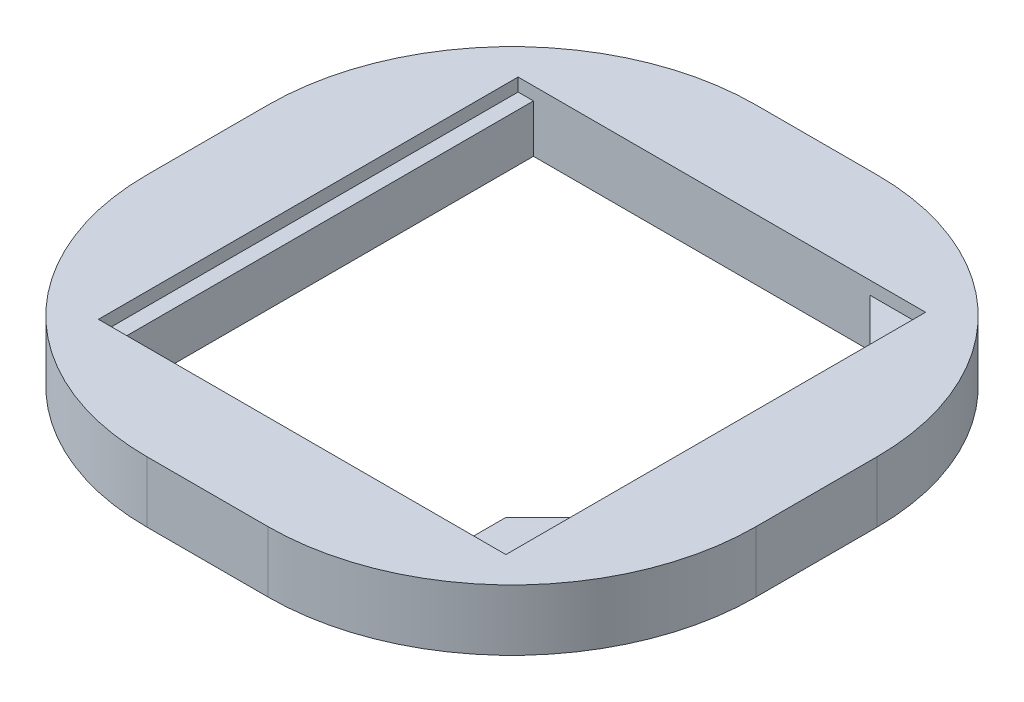
SolidWorks part; units mm, degrees
ref_plane "Front Plane" through (0, 0, 0) normal (0, 0, 1) x (1, 0, 0)
ref_plane "Top Plane" through (0, 0, 0) normal (0, 1, 0) x (1, 0, 0)
ref_plane "Right Plane" through (0, 0, 0) normal (1, 0, 0) x (0, 0, -1)
sketch "Sketch2" plane through (0, 0, 0) normal (0, 1, 0) x (1, 0, 0)
  line L1 (-37.45, -37.45) -> (37.45, -37.45)
  line L2 (-37.45, -37.45) -> (-37.45, 37.45)
  line L3 (-37.45, 37.45) -> (37.45, 37.45)
  line L4 (37.45, -37.45) -> (37.45, 37.45)
  line L5 (-37.45, -37.45) -> (37.45, 37.45) construction
  line L6 (-37.45, 37.45) -> (37.45, -37.45) construction
  point P0 (0, 0)
  dimension "D1" = 74.9
  dimension "D2" = 74.9
extrude "Base" add sketch "Sketch2" along normal blind 7.5
sketch "Sketch3" plane through (0, 7.5, 0) normal (0, 1, 0) x (1, 0, 0)
  line L1 (-25.05, -25.8) -> (25.05, -25.8)
  line L2 (-25.05, -25.8) -> (-25.05, 25.8)
  line L3 (-25.05, 25.8) -> (25.05, 25.8)
  line L4 (25.05, -25.8) -> (25.05, 25.8)
  line L5 (-25.05, -25.8) -> (25.05, 25.8) construction
  line L6 (-25.05, 25.8) -> (25.05, -25.8) construction
  point P0 (0, 0)
  dimension "D1" = 50.1
  dimension "D2" = 51.6
extrude "Slot" cut sketch "Sketch3" against normal blind 1.6
sketch "Sketch4" plane through (0, 5.9, 0) normal (0, 1, 0) x (1, 0, 0)
  line L0 (-23.1595, -25.8) -> (-23.1595, 25.8)
  line L1 (-23.1595, 25.8) -> (18.1922, 25.8)
  line L3 (18.1922, 25.8) -> (25.05, 18.9809)
  line L4 (25.05, 25.8) -> (-25.05, 25.8) construction
  line L5 (25.05, 18.9809) -> (25.05, -14.6954)
  line L6 (25.05, -25.8) -> (25.05, 25.8) construction
  line L7 (25.05, -14.6954) -> (19.4909, -20.2861)
  line L8 (19.4909, -20.2861) -> (19.4909, -25.8)
  line L9 (-25.05, -25.8) -> (25.05, -25.8) construction
  line L10 (19.4909, -25.8) -> (-23.1595, -25.8)
  line L11 (25.05, -25.8) -> (25.05, 25.8) construction
  point P2 (18.1922, 25.8)
extrude "Cut-Extrude2" cut sketch "Sketch4" against normal up to surface (5.9 mm away) up to face at (0, 0, 0)
fillet "Fillet1" radius 30 4 edges at (37.45, 3.75, -37.45) (37.45, 3.75, 37.45) (-37.45, 3.75, 37.45) (-37.45, 3.75, -37.45)
